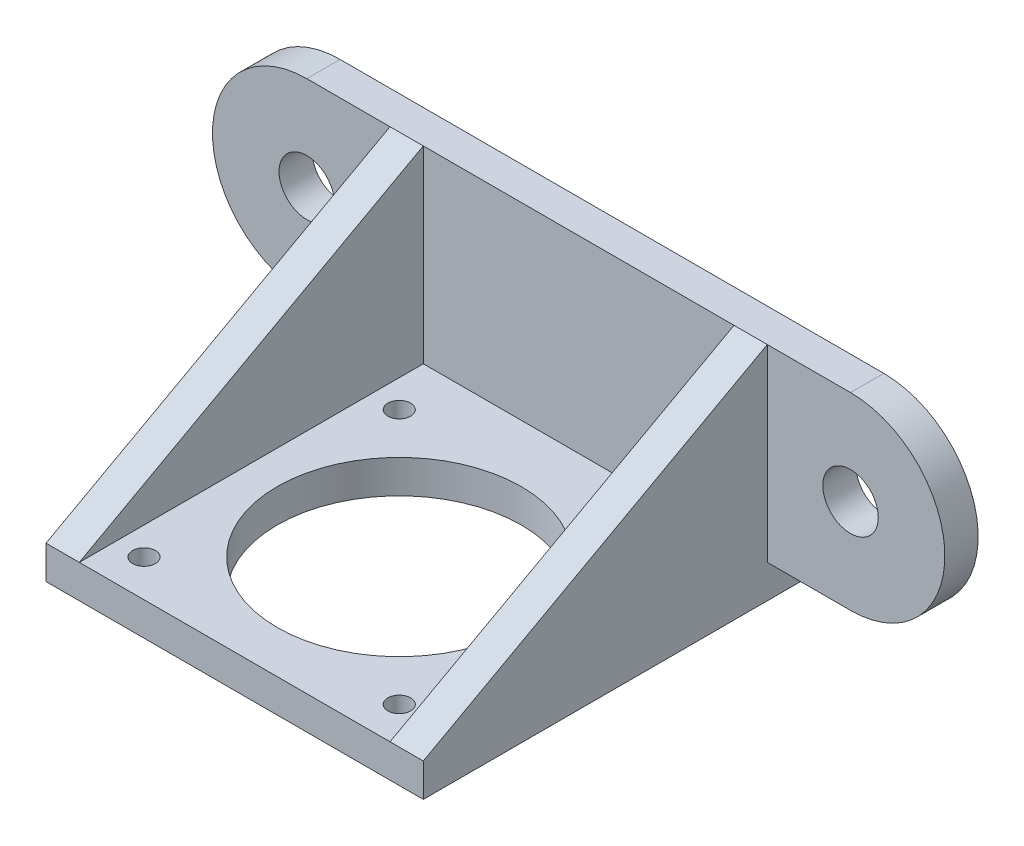
SolidWorks part; units mm, degrees
ref_plane "Front Plane" through (0, 0, 0) normal (0, 0, 1) x (1, 0, 0)
ref_plane "Top Plane" through (0, 0, 0) normal (0, 1, 0) x (1, 0, 0)
ref_plane "Right Plane" through (0, 0, 0) normal (1, 0, 0) x (0, 0, -1)
sketch "Sketch2" plane through (0, 0, 0) normal (1, 0, 0) x (0, 0, -1)
  line L0 (0, 0) -> (0, 20)
  line L1 (0, 0) -> (-34, 0)
  line L2 (-3, 3) -> (-3, 20)
  line L3 (-3, 3) -> (-34, 3)
  line L4 (0, 20) -> (-3, 20)
  line L5 (-34, 0) -> (-34, 3)
  dimension "D1" = 20
  dimension "D2" = 34
  dimension "D3" = 3
extrude "Boss-Extrude2" add sketch "Sketch2" along normal mid plane 34
sketch "Sketch5" plane through (17, 0, 0) normal (1, 0, 0) x (0, 0, -1)
  line L0 (-34, 3) -> (-3, 20)
  line L1 (-34, 3) -> (-34, 0) construction
  line L2 (-3, 3) -> (-34, 3) construction
rib "Rib2" sketch "Sketch5" sketch "Sketch5" thickness 3 extrusion direction parallel to sketch draft on no parameters "D1"=3
sketch "Sketch6" plane through (0, 0, 0) normal (0, 0, 1) x (1, 0, 0)
  line L0 (17, 0) -> (17, 20) construction
  line L1 (17, 20) -> (24.5, 20)
  line L2 (14, 3) -> (-17, 3) construction
  line L3 (14, 3) -> (-17, 3) construction
  line L4 (17, 3) -> (24.5, 3)
  line L5 (17, 3) -> (17, 20)
  circle A0 centre (24.5, 11.5) radius 2.5
  arc A1 (24.5, 20) -> (24.5, 3) centre (24.5, 11.5) cw
  point P14 (24.5, 3)
  dimension "D1" = 5
  dimension "D2" = 7.5
extrude "Boss-Extrude3" add sketch "Sketch6" along normal blind 3
mirror "Mirror1" about plane through (0, 0, 0) normal (1, 0, 0) of "Rib2", "Boss-Extrude3"
sketch "Sketch8" plane through (0, 3, 0) normal (0, 1, 0) x (1, 0, 0)
  point P0 (0, -19.3621)
  line B0 (14, -30.668) -> (14, -7.668)
  line B1 (11.5, -5.168) -> (-11.5, -5.168)
  line B2 (-14, -7.668) -> (-14, -30.668)
  line B3 (-11.5, -33.168) -> (11.5, -33.168)
  arc B4 (14, -7.668) -> (11.5, -5.168) centre (11.5, -7.668) ccw
  arc B5 (-11.5, -5.168) -> (-14, -7.668) centre (-11.5, -7.668) ccw
  arc B6 (-14, -30.668) -> (-11.5, -33.168) centre (-11.5, -30.668) ccw
  arc B7 (11.5, -33.168) -> (14, -30.668) centre (11.5, -30.668) ccw
  arc B8 (11, -19.168) -> (-11, -19.168) centre (0, -19.168) ccw
  arc B9 (-11, -19.168) -> (11, -19.168) centre (0, -19.168) ccw
  arc B10 (-12.525, -30.668) -> (-10.475, -30.668) centre (-11.5, -30.668) ccw
  arc B11 (-10.475, -30.668) -> (-12.525, -30.668) centre (-11.5, -30.668) ccw
  arc B12 (10.475, -30.668) -> (12.525, -30.668) centre (11.5, -30.668) ccw
  arc B13 (12.525, -30.668) -> (10.475, -30.668) centre (11.5, -30.668) ccw
  arc B14 (10.475, -7.668) -> (12.525, -7.668) centre (11.5, -7.668) ccw
  arc B15 (12.525, -7.668) -> (10.475, -7.668) centre (11.5, -7.668) ccw
  arc B16 (-10.475, -7.668) -> (-12.525, -7.668) centre (-11.5, -7.668) ccw
  arc B17 (-12.525, -7.668) -> (-10.475, -7.668) centre (-11.5, -7.668) ccw
  dimension "D1" = 117.5
sketch_block_instance "Block-nema11-1"
sketch_block "Block-nema11"
extrude "Cut-Extrude1" cut sketch "Sketch8" against normal up to surface (3 mm away) contours B8 B9 | B16 B17 | B10 B11 | B14 B15 | B12 B13 region at (0, 3, 19.168) region at (-11.5, 3, 30.668) region at (11.5, 3, 30.668) region at (11.5, 3, 7.668) region at (-11.5, 3, 7.668) up to face at (0, 0, 17)
